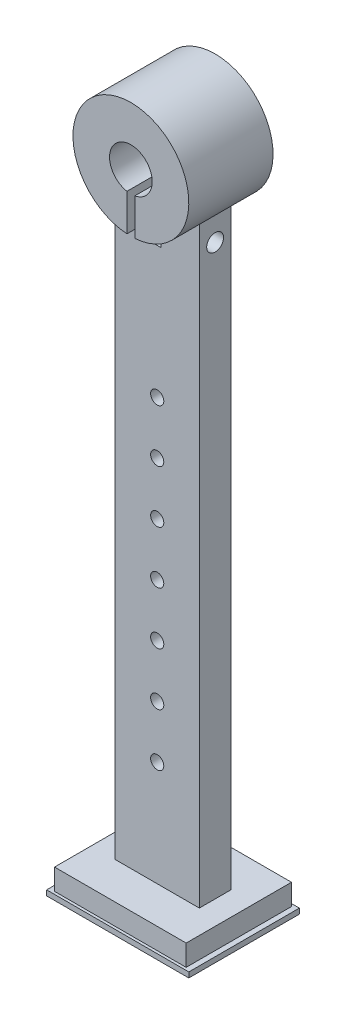
SolidWorks part; units mm, degrees
ref_plane "前视基准面" through (0, 0, 0) normal (0, 0, 1) x (1, 0, 0)
ref_plane "上视基准面" through (0, 0, 0) normal (0, 1, 0) x (1, 0, 0)
ref_plane "右视基准面" through (0, 0, 0) normal (1, 0, 0) x (0, 0, -1)
sketch "草图5" plane through (0, 0, 0) normal (0, 0, 1) x (1, 0, 0)
  line L0 (0, 22.4286) -> (0, -22.4286) construction
  line L2 (-8, -120) -> (8, -120)
  line L3 (-8, -120) -> (-8, 11)
  line L4 (-8, 11) -> (8, 11)
  line L5 (8, -120) -> (8, 11)
  circle A0 centre (0, 0) radius 11
  circle A1 centre (0, 0) radius 4.05
  point P7 (0, 0)
  dimension "D1" = 22
  dimension "D2" = 8.1
  dimension "D4" = 11
  dimension "D3" = 16
  dimension "D5" = 120
extrude "凸台-拉伸2" add sketch "草图5" along normal mid plane 16 contours L3 A0 | L0 A0 L3 A1 | A0 L0 A1 L5 | L5 A0 region at (4.1763, 0, 0) region at (-4.1763, 0, 0) region at (9.2152, 0, 0) region at (-9.2152, 0, 0)
extrude "凸台-拉伸4" add sketch "草图5<5>" along normal mid plane 6 contours A0 L3 L2 L5 region at (0, -64.9622, 0)
sketch "草图5<5>" plane through (0, 0, 0) normal (0, 0, 1) x (1, 0, 0) same geometry as "草图5"
sketch "草图6" plane through (0, 0, 0) normal (0, 0, 1) x (1, 0, 0)
  line L1 (-0.75, -3) -> (0.75, -3)
  line L2 (-0.75, -3) -> (-0.75, -15)
  line L3 (-0.75, -15) -> (0.75, -15)
  line L4 (0.75, -3) -> (0.75, -15)
  line L5 (-0.75, -3) -> (0.75, -15) construction
  line L6 (-0.75, -15) -> (0.75, -3) construction
  point P0 (0, -9)
  point P7 (0, -3)
  dimension "D1" = 1.5
  dimension "D2" = 15
  dimension "D3" = 3
extrude "切除-拉伸2" cut sketch "草图6" against normal through all both and the other way through all
sketch "草图7" plane through (0, 0, 0) normal (1, 0, 0) x (0, 0, -1)
  circle A0 centre (0, -12) radius 1.6
  dimension "D2" = 3.2
  dimension "D1" = 12
extrude "切除-拉伸3" cut sketch "草图7" against normal through all both and the other way through all
sketch "草图8" plane through (0, 0, 0) normal (0, 0, 1) x (1, 0, 0)
  line L0 (0, 0) -> (0, -126.5011) construction
  circle A0 centre (0, -40) radius 1.25
  dimension "D1" = 40
extrude "切除-拉伸4" cut sketch "草图8" against normal through all both and the other way through all
pattern_linear "阵列(线性)1" count 7 spacing 10 along (0, -1, 0) of "切除-拉伸4"
sketch "草图9" plane through (0, -120, 0) normal (0, -1, 0) x (1, 0, 0)
  line L1 (-12.5, -10) -> (12.5, -10)
  line L2 (-12.5, -10) -> (-12.5, 10)
  line L3 (-12.5, 10) -> (12.5, 10)
  line L4 (12.5, -10) -> (12.5, 10)
  line L5 (-12.5, -10) -> (12.5, 10) construction
  line L6 (-12.5, 10) -> (12.5, -10) construction
  point P0 (-2.2492, -1.7993)
  point P6 (0, 0)
  point P7 (0, 0)
  point P9 (0, 0)
  dimension "D1" = 25
extrude "凸台-拉伸5" add sketch "草图9" along normal blind 4
sketch "草图10" plane through (0, -124, 0) normal (0, -1, 0) x (1, 0, 0)
  line L0 (-13.5, -10.5) -> (-13.5, 10.5)
  line L1 (-11.5, -8.5) -> (11.5, -8.5)
  line L2 (-11.5, -8.5) -> (-11.5, 8.5)
  line L3 (-11.5, 8.5) -> (11.5, 8.5)
  line L4 (11.5, -8.5) -> (11.5, 8.5)
  line L5 (-11.5, -8.5) -> (11.5, 8.5) construction
  line L6 (-11.5, 8.5) -> (11.5, -8.5) construction
  line L7 (-13.5, 10.5) -> (13.5, 10.5)
  line L8 (13.5, -10.5) -> (13.5, 10.5)
  line L9 (-13.5, -10.5) -> (13.5, -10.5)
  point P0 (0, 0)
  dimension "D1" = 23
  dimension "D2" = 17
  dimension "D3" = 2
extrude "凸台-拉伸7" add sketch "草图10" along normal blind 1
